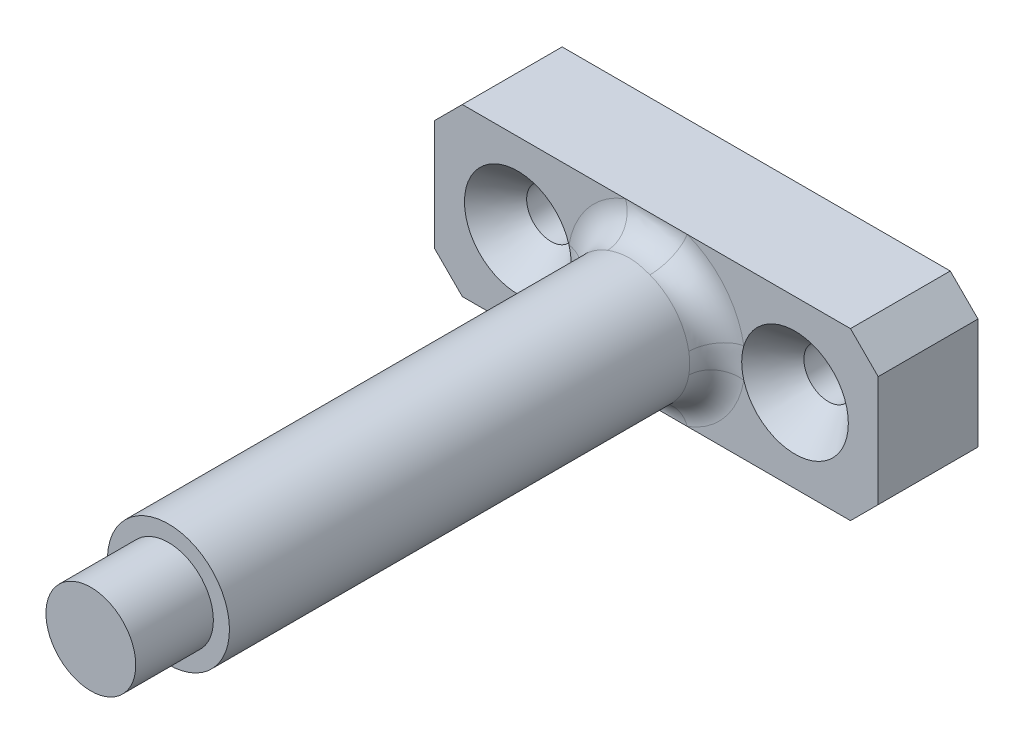
SolidWorks part; units mm, degrees
ref_plane "Front Plane" through (0, 0, 0) normal (0, 0, 1) x (1, 0, 0)
ref_plane "Top Plane" through (0, 0, 0) normal (0, 1, 0) x (1, 0, 0)
ref_plane "Right Plane" through (0, 0, 0) normal (1, 0, 0) x (0, 0, -1)
sketch "Sketch1" plane through (0, 0, 0) normal (0, 0, 1) x (1, 0, 0)
  line L0 (7.5, -7.5) -> (0, -7.5) construction
  line L1 (0, 0) -> (40, 0)
  line L2 (0, 0) -> (0, -15)
  line L3 (0, -15) -> (40, -15)
  line L4 (40, 0) -> (40, -15)
  line L5 (20, 0) -> (20, -15) construction
  circle A0 centre (7.5, -7.5) radius 2.2
  circle A1 centre (32.5, -7.5) radius 2.2
  dimension "D1" = 4.4
  dimension "D2" = 7.5
  dimension "D3" = 15
  dimension "D4" = 40
extrude "Boss-Extrude1" add sketch "Sketch1" along normal blind 9
ref_plane "Plane1" through (7.5, 0, 0) normal (1, 0, 0) x (0, 0, -1)
sketch "Sketch3" plane through (7.5, 0, 0) normal (1, 0, 0) x (0, 0, -1)
  line L0 (-9, -7.5) -> (-6, -7.5)
  line L1 (-9, -15) -> (-9, 0) construction
  line L2 (-6, -7.5) -> (-6, -9.7)
  line L3 (-6, -9.7) -> (-9, -12.3079)
  line L4 (-9, -12.3079) -> (-9, -7.5)
  dimension "D1" = 3
  dimension "D2" = 2.2
  dimension "D3" = 131
revolve "Cut-Revolve1" cut sketch "Sketch3" angle 360 about L0
ref_plane "Plane2" through (20, 0, 0) normal (1, 0, 0) x (0, 0, -1)
mirror "Mirror1" about plane through (20, 0, 0) normal (1, 0, 0) of "Cut-Revolve1"
sketch "Sketch4" plane through (0, 0, 9) normal (0, 0, 1) x (1, 0, 0)
  line L0 (20, 0) -> (20, -15) construction
  line L1 (40, 0) -> (0, 0) construction
  line L2 (0, -15) -> (40, -15) construction
  circle A0 centre (20, -7.5) radius 5.5
  point P6 (20, -7.5)
  dimension "D1" = 11
extrude "Boss-Extrude2" add sketch "Sketch4" along normal offset from surface (44 mm away) 53 up to face at (20, -7.5, 0)
sketch "Sketch5" plane through (0, 0, 53) normal (0, 0, 1) x (1, 0, 0)
  circle A0 centre (20, -7.5) radius 4.05
  dimension "D1" = 8.1
extrude "Boss-Extrude3" add sketch "Sketch5" along normal blind 7 and the other way up to surface (44 mm away) other way up to face at (25.5, -7.5, 9)
sketch "Sketch6" plane through (0, 0, 53) normal (0, 0, 1) x (1, 0, 0)
  circle A0 centre (20, -7.5) radius 2
  dimension "D1" = 4
extrude "Cut-Extrude1" cut sketch "Sketch6" against normal offset from surface 3 and the other way offset from surface 3 up to face at (20, -7.5, 0) other way up to face at (24.05, -7.5, 60)
chamfer "Chamfer1" distance 2.5 angle 45 4 edges at (40, -15, 4.5) (40, 0, 4.5) (0, 0, 4.5) (0, -15, 4.5)
fillet "Fillet1" radius 2.5 1 edges at (25.5, -7.5, 9)
